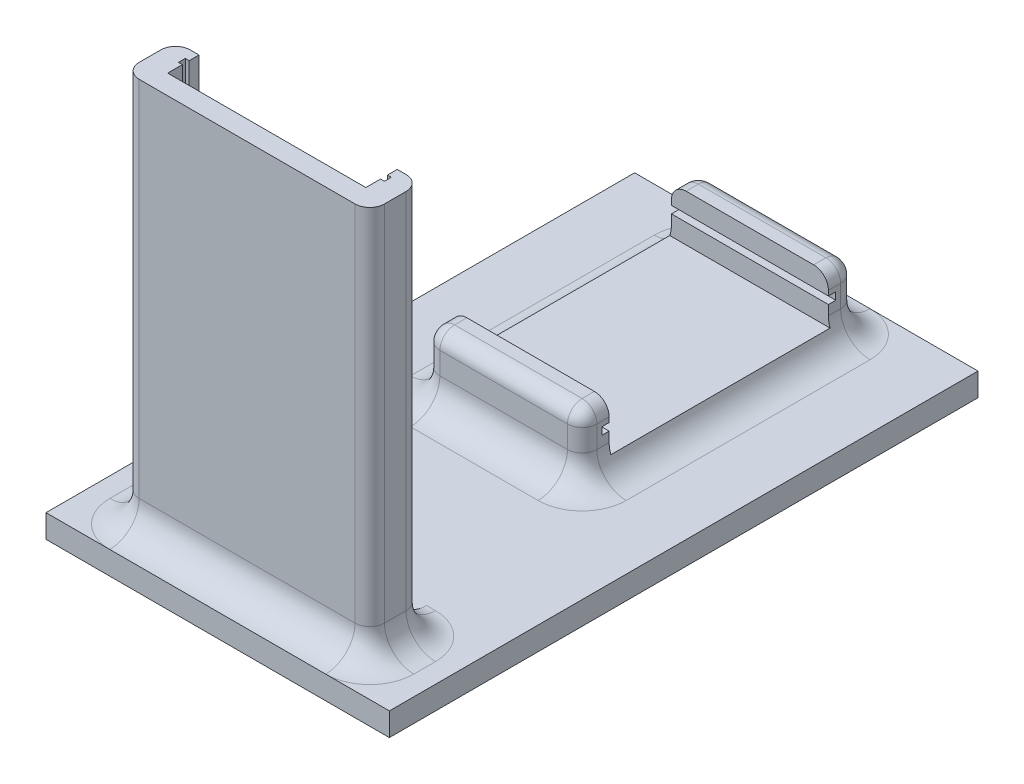
SolidWorks part; units mm, degrees
material "Melamine resin"
ref_plane "Front Plane" through (0, 0, 0) normal (0, 0, 1) x (1, 0, 0)
ref_plane "Top Plane" through (0, 0, 0) normal (0, 1, 0) x (1, 0, 0)
ref_plane "Right Plane" through (0, 0, 0) normal (1, 0, 0) x (0, 0, -1)
sketch "Sketch2" plane through (0, 0, 0) normal (0, 1, 0) x (1, 0, 0)
  line L1 (0, 0) -> (88.9, 0)
  line L2 (0, 0) -> (0, 152.4)
  line L3 (0, 152.4) -> (88.9, 152.4)
  line L10 (88.9, 152.4) -> (88.9, 0)
  dimension "D1" = 152.4
  dimension "D2" = 88.9
extrude "Boss-Extrude1" add sketch "Sketch2" along normal blind 5.9944 contours L3 L10 L1 L2
sketch "Sketch4" plane through (0, 5.9944, 0) normal (0, 1, 0) x (1, 0, 0)
  line L0 (0, 0) -> (0, 152.4) construction
  line L1 (0, 0) -> (88.9, 0) construction
  circle A0 centre (45.72, 109.8713) radius 2.7305
  circle A1 centre (45.72, 33.6713) radius 2.7305
  dimension "D3" = 5.461
  dimension "D4" = 5.461
  dimension "D1" = 76.2
  dimension "D2" = 45.72
  dimension "D5" = 33.6713
extrude "Cut-Extrude2" cut sketch "Sketch4" against normal through all both
sketch "Sketch5" plane through (0, 5.9944, 0) normal (0, 1, 0) x (1, 0, 0)
  line L0 (0, 152.4) -> (88.9, 152.4) construction
  line L1 (12.7, 20.828) -> (76.2, 20.828)
  line L2 (12.7, 20.828) -> (12.7, 7.62)
  line L3 (12.7, 7.62) -> (76.2, 7.62)
  line L4 (76.2, 20.828) -> (76.2, 7.62)
  line L5 (18.796, 12.7) -> (70.104, 12.7)
  line L6 (18.796, 12.7) -> (18.796, 20.828)
  line L7 (18.796, 20.828) -> (70.104, 20.828)
  line L8 (70.104, 12.7) -> (70.104, 20.828)
  line L9 (17.78, 18.288) -> (71.12, 18.288)
  line L10 (17.78, 18.288) -> (17.78, 16.51)
  line L11 (17.78, 16.51) -> (71.12, 16.51)
  line L12 (71.12, 18.288) -> (71.12, 16.51)
  line L13 (0, 0) -> (88.9, 0) construction
  point P12 (71.8842, 128.6711)
  point P13 (79.7243, 141.8754)
  point P16 (44.45, 152.4)
  point P17 (44.45, 20.828)
  point P18 (18.796, 127.6717)
  point P19 (0, 0)
  point P20 (18.796, 129.3154)
  point P21 (18.796, 131.8443)
  dimension "D1" = 53.34
  dimension "D2" = 1.016
  dimension "D3" = 1.016
  dimension "D4" = 3.81
  dimension "D5" = 2.54
  dimension "D6" = 5.08
  dimension "D7" = 5.08
  dimension "D8" = 1.778
  dimension "D9" = 7.62
  dimension "D10" = 5.08
extrude "Boss-Extrude2" add sketch "Sketch5" along normal blind 101.6 contours L9 L12 L11 L8 L5 L6 L10 L1 L2 L3 L4 region at (44.45, 5.9944, -11.6628)
fillet "Fillet1" radius 3.81 4 edges at (12.7, 56.7944, -7.62) (12.7, 56.7944, -20.828) (76.2, 56.7944, -7.62) (76.2, 56.7944, -20.828)
fillet "Fillet2" radius 7.62 9 edges at (17.653, 5.9944, -20.828) (13.8159, 5.9944, -19.7121) (12.7, 5.9944, -14.224) (13.8159, 5.9944, -8.7359) (71.247, 5.9944, -20.828) (75.0841, 5.9944, -19.7121) (76.2, 5.9944, -14.224) (75.0841, 5.9944, -8.7359) (44.45, 5.9944, -7.62)
ref_plane "Plane1" through (44.45, 0, 0) normal (-1, 0, 0) x (0, 0, 1)
sketch "Sketch6" plane through (44.45, 0, 0) normal (-1, 0, 0) x (0, 0, 1)
  line L0 (0, 5.9944) -> (-152.4, 5.9944) construction
  line L1 (0, 5.9944) -> (-152.4, 5.9944)
  line L3 (-144.78, 5.9944) -> (-74.041, 5.9944)
  line L4 (-144.78, 5.9944) -> (-144.78, 23.1394)
  line L5 (-144.78, 23.1394) -> (-74.041, 23.1394)
  line L6 (-74.041, 5.9944) -> (-74.041, 23.1394)
  line L7 (-137.795, 23.1394) -> (-81.026, 23.1394)
  line L8 (-137.795, 23.1394) -> (-137.795, 11.0744)
  line L9 (-137.795, 11.0744) -> (-81.026, 11.0744)
  line L10 (-81.026, 23.1394) -> (-81.026, 11.0744)
  line L11 (-139.7, 18.0594) -> (-79.121, 18.0594)
  line L12 (-139.7, 18.0594) -> (-139.7, 16.1544)
  line L13 (-139.7, 16.1544) -> (-79.121, 16.1544)
  line L14 (-79.121, 18.0594) -> (-79.121, 16.1544)
  line L15 (-152.4, 5.9944) -> (-152.4, 0) construction
  point P16 (0, 0)
  dimension "D1" = 60.579
  dimension "D2" = 1.905
  dimension "D3" = 1.905
  dimension "D4" = 1.905
  dimension "D5" = 5.08
  dimension "D6" = 5.08
  dimension "D7" = 5.08
  dimension "D8" = 5.08
  dimension "D9" = 5.08
  dimension "D10" = 7.62
extrude "Boss-Extrude3" add sketch "Sketch6" along normal mid plane 40.64 contours L11 L14 L13 L10 L9 L8 L12 L5 L4 L1 L6 region at (44.45, 6.7223, -109.4105)
fillet "Fillet3" radius 3.81 2 edges at (44.45, 23.1394, -74.041) (44.45, 23.1394, -144.78)
fillet "Fillet6" radius 3.81 12 edges at (24.13, 23.1394, -79.4385) (24.13, 22.0235, -75.1569) (64.77, 23.1394, -79.4385) (64.77, 22.0235, -75.1569) (64.77, 23.1394, -139.3825) (64.77, 22.0235, -143.6641) (24.13, 23.1394, -139.3825) (24.13, 22.0235, -143.6641) (24.13, 12.6619, -74.041) (64.77, 12.6619, -74.041) (64.77, 12.6619, -144.78) (24.13, 12.6619, -144.78)
fillet "Fillet7" radius 7.62 8 edges at (25.2459, 5.9944, -75.1569) (44.45, 5.9944, -74.041) (63.6541, 5.9944, -75.1569) (64.77, 5.9944, -109.4105) (63.6541, 5.9944, -143.6641) (44.45, 5.9944, -144.78) (25.2459, 5.9944, -143.6641) (24.13, 5.9944, -109.4105)
equation "\"threaded_insert_hole\"=0.1472"
equation "\"th\"=1.25249"
